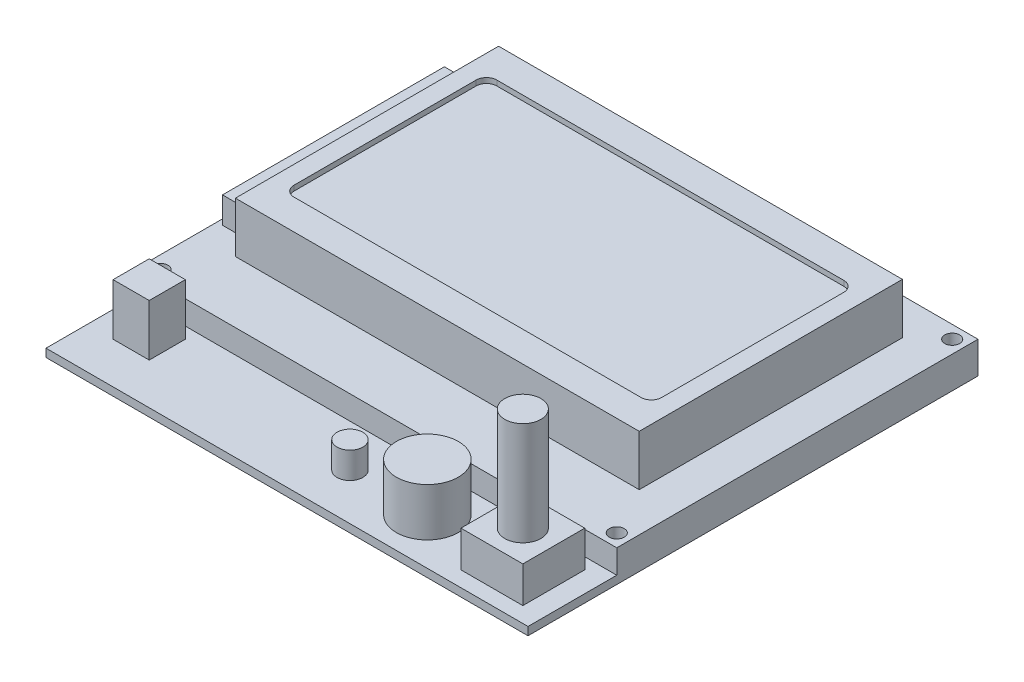
SolidWorks part; units mm, degrees
ref_plane "Front Plane" through (0, 0, 0) normal (0, 0, 1) x (1, 0, 0)
ref_plane "Top Plane" through (0, 0, 0) normal (0, 1, 0) x (1, 0, 0)
ref_plane "Right Plane" through (0, 0, 0) normal (1, 0, 0) x (0, 0, -1)
sketch "Sketch1" plane through (0, 0, 0) normal (0, 1, 0) x (1, 0, 0)
  line L0 (-46.7, 43.6) -> (46.7, -43.6) construction
  line L1 (-46.7, 43.6) -> (46.7, 43.6)
  line L2 (-46.7, 43.6) -> (-46.7, -43.6)
  line L3 (-46.7, -43.6) -> (46.7, -43.6)
  line L4 (46.7, 43.6) -> (46.7, -43.6)
  line L5 (-46.7, -34.6) -> (46.7, -34.6) construction
  line L6 (-39.125, 36.5278) -> (39.125, 36.5278)
  line L7 (-39.125, 36.5278) -> (-39.125, -14.4722)
  line L8 (-39.125, -14.4722) -> (39.125, -14.4722)
  line L9 (39.125, 36.5278) -> (39.125, -14.4722)
  line L10 (0, 43.6) -> (0, -43.6) construction
  line L11 (-45.1398, 11.0278) -> (42.9387, 11.0278) construction
  line L12 (-45.625, 32.5278) -> (-39.125, 32.5278)
  line L13 (-45.625, 32.5278) -> (-45.625, -10.4722)
  line L14 (-45.625, -10.4722) -> (-39.125, -10.4722)
  line L15 (-39.125, 32.5278) -> (-39.125, -10.4722)
  line L16 (30.7, -40.6) -> (42.7, -28.6) construction
  line L17 (30.7, -28.6) -> (42.7, -28.6)
  line L18 (30.7, -28.6) -> (30.7, -40.6)
  line L19 (30.7, -40.6) -> (42.7, -40.6)
  line L20 (42.7, -28.6) -> (42.7, -40.6)
  line L21 (44.2, 41.1) -> (44.2, -23.9) construction
  line L22 (44.2, 41.1) -> (-44.2, 41.1) construction
  line L23 (-44.2, 41.1) -> (-44.2, -23.9) construction
  line L24 (44.2, -23.9) -> (-44.2, -23.9) construction
  line L26 (-46.7, 43.6) -> (46.7, 43.6)
  line L27 (-46.7, 43.6) -> (-46.7, -26.4)
  line L28 (-46.7, -26.4) -> (46.7, -26.4)
  line L29 (46.7, 43.6) -> (46.7, -26.4)
  circle A0 centre (36.7, -34.6) radius 3.5
  circle A1 centre (18.2, -34.6) radius 6
  circle A2 centre (3.2, -34.6) radius 2.5
  circle A3 centre (44.2, 41.1) radius 1.45
  circle A4 centre (44.2, -23.9) radius 1.45
  circle A5 centre (-44.2, 41.1) radius 1.45
  circle A6 centre (-44.2, -23.9) radius 1.45
  point P4 (0, 0)
  point P18 (0, 36.5278)
  point P28 (-45.625, 11.0278)
  point P29 (-39.125, 11.0278)
  point P35 (36.7, -34.6)
  dimension "D10" = 7
  dimension "D12" = 12
  dimension "D15" = 5
  dimension "D16" = 2.9
  dimension "D17" = 2.5
  dimension "D1" = 93.4
  dimension "D2" = 87.2
  dimension "D3" = 9
  dimension "D4" = 78.25
  dimension "D5" = 51
  dimension "D6" = 6.5
  dimension "D7" = 43
  dimension "D8" = 12
  dimension "D9" = 12
  dimension "D11" = 18.5
  dimension "D13" = 15
  dimension "D14" = 10
  dimension "D18" = 2.5
  dimension "D19" = 2.5
  dimension "D20" = 70
  dimension "D21" = 2.5
extrude "Boss-Extrude2" add sketch "Sketch1" against normal blind 1.57 contours L28 L2 L3 L4 A2 A1 L17 L20 L19 L18 | L2 L28 L4 L1 A6 A5 A4 A3 L14 L13 L12 L7 L6 L9 L8 | L13 L14 L7 L12 | L9 L6 L7 L8 | A2 | A1 | L20 L17 L18 L19 A0 | A0 region at (0, 0, -42.4328) region at (-5.5695, 0, 35.0832) region at (0, 0, -11.0278) region at (-42.375, 0, -11.0278) region at (36.7, 0, 28.7697) region at (36.7, 0, 34.6) region at (18.2, 0, 34.6) region at (3.2, 0, 34.6)
extrude "Boss-Extrude3" add sketch "Sketch1<3>" along normal blind 4.6 contours L2 L28 L4 L1 A6 A5 A4 A3 L14 L13 L12 L7 L6 L9 L8 | L13 L14 L7 L12 | L9 L6 L7 L8 region at (0, 0, -42.4328) region at (0, 0, -11.0278) region at (-42.375, 0, -11.0278)
sketch "Sketch1<3>" plane through (0, 0, 0) normal (0, 1, 0) x (1, 0, 0) same geometry as "Sketch1"
extrude "Boss-Extrude4" add sketch "Sketch1<4>" along normal blind 14.4 contours L8 L9 L6 L7
sketch "Sketch1<4>" plane through (0, 0, 0) normal (0, 1, 0) x (1, 0, 0) same geometry as "Sketch1"
extrude "Boss-Extrude5" add sketch "Sketch1<5>" along normal blind 9.7 contours L14 L15 L12 L13
sketch "Sketch1<5>" plane through (0, 0, 0) normal (0, 1, 0) x (1, 0, 0) same geometry as "Sketch1"
extrude "Boss-Extrude6" add sketch "Sketch1<6>" along normal blind 7 contours L19 L20 L17 L18
sketch "Sketch1<6>" plane through (0, 0, 0) normal (0, 1, 0) x (1, 0, 0) same geometry as "Sketch1"
extrude "Boss-Extrude7" add sketch "Sketch1<7>" along normal blind 27 contours A0
sketch "Sketch1<7>" plane through (0, 0, 0) normal (0, 1, 0) x (1, 0, 0) same geometry as "Sketch1"
extrude "Boss-Extrude8" add sketch "Sketch1<8>" along normal blind 9.3 contours A1
sketch "Sketch1<8>" plane through (0, 0, 0) normal (0, 1, 0) x (1, 0, 0) same geometry as "Sketch1"
extrude "Boss-Extrude9" add sketch "Sketch1<9>" along normal blind 5.1 contours A2
sketch "Sketch1<9>" plane through (0, 0, 0) normal (0, 1, 0) x (1, 0, 0) same geometry as "Sketch1"
sketch "Sketch3" plane through (0, -1.57, 0) normal (0, -1, 0) x (1, 0, 0)
  line L0 (-46.7, -43.6) -> (46.7, -43.6) construction
  line L1 (-46.7, -21.64) -> (-20.44, -21.64)
  line L2 (-46.7, -21.64) -> (-46.7, 4.83)
  line L3 (-46.7, 4.83) -> (-20.44, 4.83)
  line L4 (-20.44, -21.64) -> (-20.44, 4.83)
  line L5 (-46.7, -43.6) -> (-46.7, 43.6) construction
  dimension "D1" = 26.47
  dimension "D2" = 26.26
  dimension "D3" = 48.43
extrude "Boss-Extrude10" add sketch "Sketch3" along normal blind 4
sketch "Sketch4" plane through (0, -1.57, 0) normal (0, -1, 0) x (1, 0, 0)
  line L0 (46.7, -43.6) -> (46.7, 43.6) construction
  line L1 (-25.32, -28.2) -> (-5.04, -28.2)
  line L2 (-25.32, -28.2) -> (-25.32, -37.2)
  line L3 (-25.32, -37.2) -> (-5.04, -37.2)
  line L4 (-5.04, -28.2) -> (-5.04, -37.2)
  line L5 (5.3, -28.2) -> (25.58, -28.2)
  line L6 (5.3, -28.2) -> (5.3, -37.2)
  line L7 (5.3, -37.2) -> (25.58, -37.2)
  line L8 (25.58, -28.2) -> (25.58, -37.2)
  line L10 (-46.7, -43.6) -> (46.7, -43.6) construction
  point P10 (25.58, -32.7)
  dimension "D1" = 9
  dimension "D2" = 20.28
  dimension "D3" = 50.9
  dimension "D4" = 41.4
  dimension "D5" = 15.4
extrude "Boss-Extrude11" add sketch "Sketch4" along normal blind 20
sketch "Sketch5" plane through (0, 14.4, 0) normal (0, 1, 0) x (1, 0, 0)
  line L0 (-39.125, 36.5278) -> (-39.125, -14.4722) construction
  line L1 (33.625, 30.6778) -> (-33.625, 30.6778)
  line L2 (35.625, 28.6778) -> (35.625, -6.6222)
  line L3 (33.625, -8.6222) -> (-33.625, -8.6222)
  line L4 (-35.625, 28.6778) -> (-35.625, -6.6222)
  line L5 (39.125, 36.5278) -> (39.125, -14.4722) construction
  line L6 (-39.125, 36.5278) -> (39.125, 36.5278) construction
  line L7 (-39.125, -14.4722) -> (39.125, -14.4722) construction
  arc A0 (33.625, 30.6778) -> (35.625, 28.6778) centre (33.625, 28.6778) cw
  arc A1 (35.625, -6.6222) -> (33.625, -8.6222) centre (33.625, -6.6222) cw
  arc A2 (-33.625, -8.6222) -> (-35.625, -6.6222) centre (-33.625, -6.6222) cw
  arc A3 (-33.625, 30.6778) -> (-35.625, 28.6778) centre (-33.625, 28.6778) ccw
  dimension "D5" = 2
  dimension "D1" = 3.5
  dimension "D2" = 3.5
  dimension "D3" = 5.85
  dimension "D4" = 5.85
extrude "Cut-Extrude1" cut sketch "Sketch5" against normal blind 1
sketch "Sketch6" plane through (-46.7, 0, 0) normal (-1, 0, 0) x (0, 0, 1)
  line L1 (-21.64, -5.57) -> (4.83, -5.57)
  line L2 (-21.64, -5.57) -> (-21.64, -1.57)
  line L3 (-21.64, -1.57) -> (4.83, -1.57)
  line L4 (4.83, -5.57) -> (4.83, -1.57)
extrude "Cut-Extrude2" cut sketch "Sketch6" against normal blind 1
sketch "Sketch7" plane through (0, 0, 0) normal (0, 1, 0) x (1, 0, 0)
  line L0 (-46.7, -26.4) -> (-46.7, -43.6) construction
  line L1 (-34.7, -28.6) -> (-41.7, -28.6)
  line L2 (-34.7, -28.6) -> (-34.7, -35.6)
  line L3 (-34.7, -35.6) -> (-41.7, -35.6)
  line L4 (-41.7, -28.6) -> (-41.7, -35.6)
  line L5 (-46.7, -43.6) -> (46.7, -43.6) construction
  point P4 (-41.7, -32.1)
  dimension "D1" = 7
  dimension "D2" = 7
  dimension "D3" = 5
  dimension "D4" = 8
extrude "Boss-Extrude12" add sketch "Sketch7" along normal blind 10
